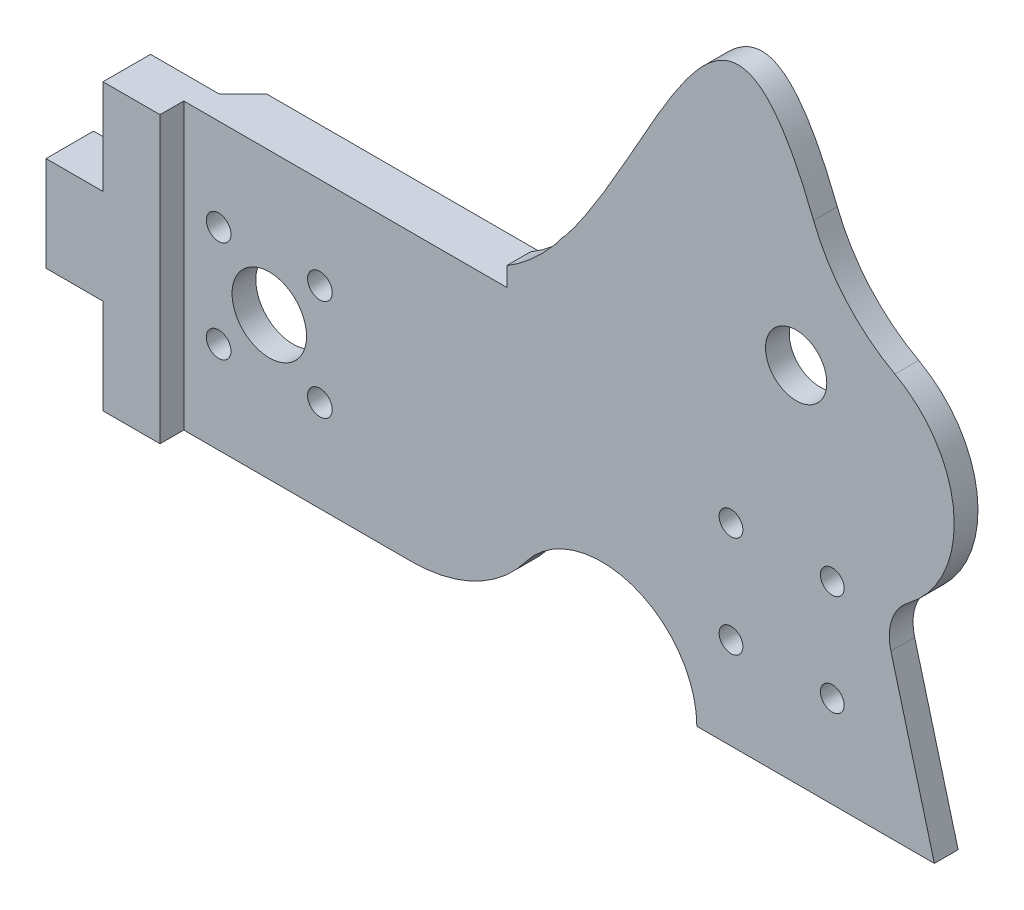
SolidWorks part; units mm, degrees
ref_plane "Front Plane" through (0, 0, 0) normal (0, 0, 1) x (1, 0, 0)
ref_plane "Top Plane" through (0, 0, 0) normal (0, 1, 0) x (1, 0, 0)
ref_plane "Right Plane" through (0, 0, 0) normal (1, 0, 0) x (0, 0, -1)
sketch "Sketch1" plane through (0, 0, 0) normal (0, 0, 1) x (1, 0, 0)
  line L0 (0, 0) -> (107.95, 0)
  line L3 (0, 38.1) -> (0, 25.4)
  line L4 (95.3675, 55.88) -> (0, 38.1)
  line L5 (0, 19.05) -> (100.2273, 19.05) construction
  line L6 (19.05, 19.05) -> (19.05, 28.62) construction
  line L7 (19.05, 19.05) -> (25.817, 25.817) construction
  line L8 (107.95, 0) -> (100.9363, 26.1756)
  line L10 (0, 12.7) -> (0, 0)
  line L11 (0, 25.4) -> (-7.62, 25.4)
  line L13 (0, 12.7) -> (-7.62, 12.7)
  line L14 (-7.62, 25.4) -> (-7.62, 12.7)
  line L15 (100.9363, 26.1756) -> (100.8688, 26.4276)
  arc A0 (100.8688, 26.4276) -> (95.3675, 55.88) centre (95.3675, 40.64) ccw
  circle A1 centre (95.3675, 40.64) radius 4.0957 construction
  circle A2 centre (19.05, 19.05) radius 9.57 construction
  circle A3 centre (25.817, 25.817) radius 1.651
  circle A4 centre (25.817, 12.283) radius 1.651
  circle A5 centre (12.283, 12.283) radius 1.651
  circle A6 centre (12.283, 25.817) radius 1.651
  point P26 (19.05, 19.05)
  dimension "D1" = 8.1915
  dimension "D5" = 15.24
  dimension "D4" = 19.14
  dimension "D7" = 3.302
  dimension "D11" = 97.0107
  dimension "D2" = 38.1
  dimension "D3" = 40.64
  dimension "D6" = 107.95
  dimension "D8" = 45
  dimension "D9" = 4
  dimension "D10" = 19.05
  dimension "D12" = 75
  dimension "D14" = 12.7
  dimension "D15" = 12.7
  dimension "D16" = 7.62
extrude "Boss-Extrude1" add sketch "Sketch1" along normal blind 3.175
sketch "Sketch2" plane through (0, 0, 3.175) normal (0, 0, 1) x (1, 0, 0)
  circle A0 centre (95.3675, 40.64) radius 38.1 construction
sketch "Sketch6" plane through (0, 0, 3.175) normal (0, 0, 1) x (1, 0, 0)
  line L0 (0, 0) -> (107.95, 0) construction
  line L1 (50.8, 0) -> (76.2, 0)
  arc A0 (76.2, 0) -> (50.8, 0) centre (63.5, 0) ccw
  dimension "D1" = 25.4
  dimension "D2" = 31.75
extrude "Cut-Extrude2" cut sketch "Sketch6" against normal blind 6.35
sketch "Sketch7" plane through (0, 0, 3.175) normal (0, 0, 1) x (1, 0, 0)
  line L0 (12.283, 25.817) -> (25.817, 12.283) construction
  line L1 (12.283, 12.283) -> (25.817, 25.817) construction
  line L2 (12.283, 25.817) -> (78.4839, 25.817) construction
  line L3 (11.7326, 12.283) -> (12.283, 12.283) construction
  circle A0 centre (19.05, 19.05) radius 4.9784
  circle A4 centre (80.7666, 12.283) radius 1.5875
  circle A5 centre (94.2997, 12.283) radius 1.5875
  circle A6 centre (80.7666, 25.817) radius 1.5875
  circle A7 centre (94.2997, 25.817) radius 1.5875
  dimension "D1" = 9.9568
  dimension "D2" = 3.175
  dimension "D3" = 13.5331
extrude "Cut-Extrude3" cut sketch "Sketch7" against normal through all
fillet "Fillet1" radius 6.35 1 edges at (100.8688, 26.4276, 1.5875)
sketch "Sketch8" plane through (0, 0, 3.175) normal (0, 0, 1) x (1, 0, 0)
  line L1 (0, 38.1) -> (50.8, 38.1)
  line L2 (0, 38.1) -> (0, 50.8)
  line L3 (0, 50.8) -> (50.8, 50.8)
  line L4 (50.8, 38.1) -> (50.8, 50.8)
  dimension "D1" = 50.8
  dimension "D2" = 12.7
extrude "Cut-Extrude4" cut sketch "Sketch8" against normal blind 50.8
sketch "Sketch9" plane through (0, 0, 3.175) normal (0, 0, 1) x (1, 0, 0)
  line L3 (50.8, 40.64) -> (57.15, 40.64)
  line L5 (57.15, 40.64) -> (50.8, 40.64)
  line L6 (57.15, 40.64) -> (57.15, 50.8)
  line L7 (57.15, 50.8) -> (50.8, 50.8)
  line L8 (50.8, 40.64) -> (50.8, 50.8)
  line L9 (0, 38.1) -> (50.8, 38.1) construction
  line M8 (50.8, 47.571) -> (50.8, 38.1)
  line M21 (95.3675, 55.88) -> (50.8, 47.571)
  dimension "D1" = 10.16
  dimension "D2" = 2.54
  dimension "D3" = 6.35
extrude "Cut-Extrude5" cut sketch "Sketch9" against normal blind 19.304 contours L3 L6 M21 M8 region at (54.0583, 44.4092, 3.175)
fillet "Fillet6" radius 6.35 1 edges at (57.15, 40.64, 1.5875)
fillet "Fillet7" radius 6.35 1 edges at (57.15, 48.7549, 1.5875)
fillet "Fillet8" radius 19.05 1 edges at (50.8, 0, 1.5875)
sketch "Sketch12" plane through (0, 0, 3.175) normal (0, 0, 1) x (1, 0, 0)
  line L0 (107.95, 0) -> (146.812, 0) construction
  line L1 (8.0257, 45.4128) -> (80.6683, 75.7903) construction
  line L2 (95.3675, 40.64) -> (80.6683, 75.7903) construction
  line L3 (80.6683, 75.7903) -> (79.4434, 78.7195) construction
  line L4 (50.8, 40.64) -> (85.0271, 40.64)
  line L5 (85.0271, 40.64) -> (95.3675, 55.88)
  arc A0 (61.8128, 49.6242) -> (56.8883, 45.1859) centre (62.9766, 43.3817) ccw construction
  circle A1 centre (19.05, 19.05) radius 28.575 construction
  circle A2 centre (95.3675, 40.64) radius 38.1 construction
  circle A3 centre (80.6683, 75.7903) radius 3.175 construction
  spline S0 degree 3 poles (50.8, 40.64) (70.7778, 52.1788) (78.5943, 111.5434) (95.3675, 55.88) knots 0 0 0 0 1 1 1 1
  dimension "D2" = 6.35
  dimension "D1" = 38.862
extrude "Boss-Extrude2" add sketch "Sketch12" against normal blind 3.175
fillet "Fillet9" radius 24.13 1 edges at (95.3675, 55.88, 1.5875)
sketch "Sketch13" plane through (0, 0, 0) normal (0, 0, -1) x (-1, 0, 0)
  line L1 (-50.8, 38.1) -> (-9.1321, 38.1)
  line L2 (-50.8, 38.1) -> (-50.8, 28.6404)
  line L3 (-50.8, 28.6404) -> (-9.1321, 28.6404)
  line L6 (-9.1321, 8.4682) -> (-38.1, 8.4682)
  line L7 (-9.1321, 8.4682) -> (-9.1321, 0)
  line L8 (-9.1321, 0) -> (-38.1, 0)
  line L9 (-38.1, 8.4682) -> (-38.1, 0)
  line L10 (-9.1321, 38.1) -> (-9.1321, 28.6404)
  point P3 (0, 8.4682)
  point P5 (0, 0)
extrude "Boss-Extrude3" add sketch "Sketch13" along normal blind 3.175
sketch "Sketch16" plane through (0, 0, 3.175) normal (0, 0, 1) x (1, 0, 0)
  circle A0 centre (89.4737, 48.423) radius 4.0958
  circle A1 centre (94.2997, 25.817) radius 1.5875 construction
  dimension "D1" = 22.606
  dimension "D2" = 4.826
extrude "Cut-Extrude8" cut sketch "Sketch16" against normal through all
sketch "Sketch18" plane through (0, 0, 3.175) normal (0, 0, 1) x (1, 0, 0)
  line L0 (0, 0) -> (7.62, 0)
  line L1 (0, 0) -> (38.1, 0) construction
  line L2 (7.62, 0) -> (7.62, 38.1)
  line L3 (0, 38.1) -> (50.8, 38.1) construction
  line L4 (7.62, 38.1) -> (0, 38.1)
  line L5 (0, 38.1) -> (0, 25.4)
  line L6 (0, 25.4) -> (-7.62, 25.4)
  line L7 (-7.62, 25.4) -> (-7.62, 12.7)
  line L8 (-7.62, 12.7) -> (0, 12.7)
  line L9 (0, 12.7) -> (0, 0)
  point P17 (0, 25.4)
  dimension "D1" = 7.62
extrude "Boss-Extrude4" add sketch "Sketch18" along normal blind 3.175
sketch "Sketch19" plane through (0, 38.1, 0) normal (0, 1, 0) x (1, 0, 0)
  line L0 (9.1321, 0) -> (12.3071, 3.175)
  line L1 (9.1321, 3.175) -> (50.8, 3.175) construction
  line L2 (9.1321, 3.175) -> (9.1321, 0) construction
  line L3 (12.3071, 3.175) -> (9.1321, 3.175)
  line L4 (9.1321, 3.175) -> (9.1321, 0)
  point P7 (9.1321, -0.0554)
  point P10 (9.1321, 3.175)
  dimension "D1" = 45
extrude "Cut-Extrude9" cut sketch "Sketch19" against normal through all
